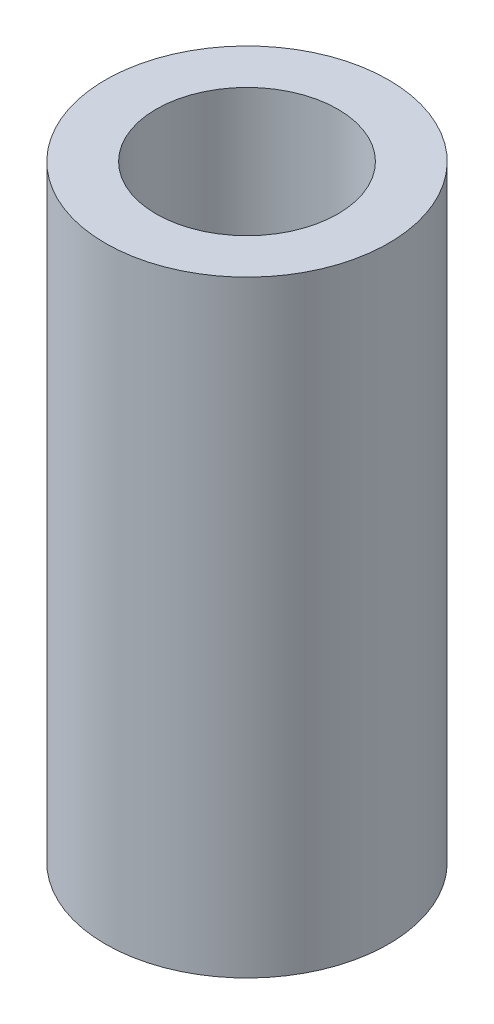
SolidWorks part; units mm, degrees
ref_plane "Front Plane" through (0, 0, 0) normal (0, 0, 1) x (1, 0, 0)
ref_plane "Top Plane" through (0, 0, 0) normal (0, 1, 0) x (1, 0, 0)
ref_plane "Right Plane" through (0, 0, 0) normal (1, 0, 0) x (0, 0, -1)
sketch "Sketch1" plane through (0, 0, 0) normal (0, 1, 0) x (1, 0, 0)
  circle A0 centre (0, 0) radius 7.5
  dimension "SLEEVE_OD" = 15
extrude "Boss-Extrude1" add sketch "Sketch1" along normal blind 32.1558
sketch "Sketch2" plane through (0, 0, 0) normal (0, 1, 0) x (1, 0, 0)
  circle A0 centre (0, 0) radius 4.8122
  dimension "BORE_D" = 9.6244
extrude "Cut-Extrude1" cut sketch "Sketch2" along normal through all
chamfer "Chamfer1" distance 1.0826 angle 60 rebuild error yes
